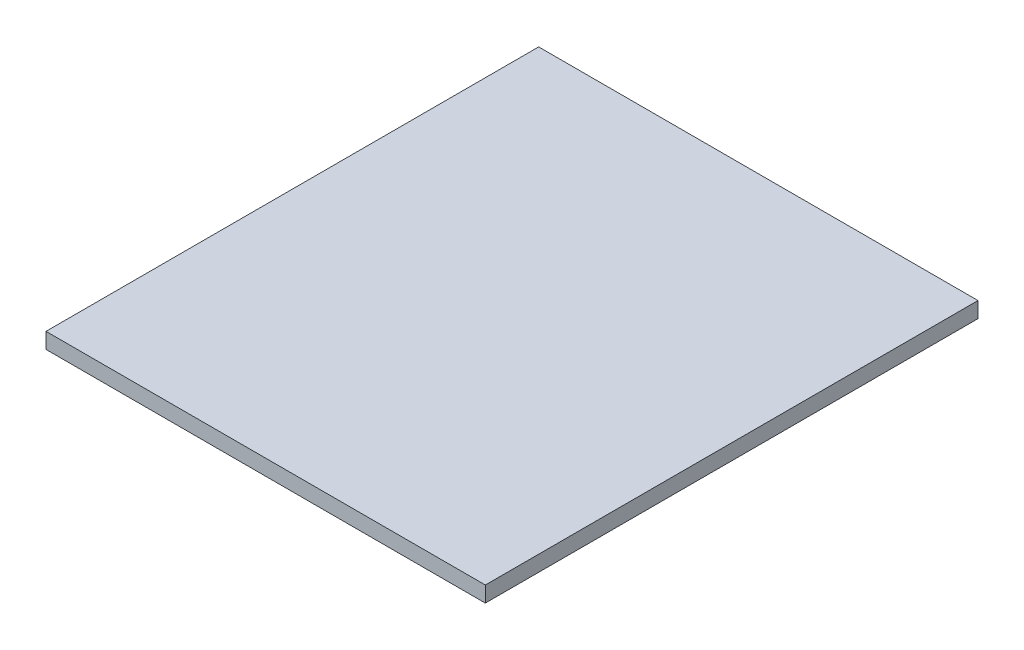
SolidWorks part; units mm, degrees
ref_plane "Front Plane" through (0, 0, 0) normal (0, 0, 1) x (1, 0, 0)
ref_plane "Top Plane" through (0, 0, 0) normal (0, 1, 0) x (1, 0, 0)
ref_plane "Right Plane" through (0, 0, 0) normal (1, 0, 0) x (0, 0, -1)
sketch "Sketch1" plane through (0, 0, 0) normal (0, 1, 0) x (1, 0, 0)
  line L1 (280, -314) -> (-280, -314)
  line L2 (280, -314) -> (280, 314)
  line L3 (280, 314) -> (-280, 314)
  line L4 (-280, -314) -> (-280, 314)
  line L5 (280, -314) -> (-280, 314) construction
  line L6 (280, 314) -> (-280, -314) construction
  point P0 (0, 0)
  dimension "D1" = 628
  dimension "D2" = 560
extrude "Boss-Extrude1" add sketch "Sketch1" along normal blind 20
